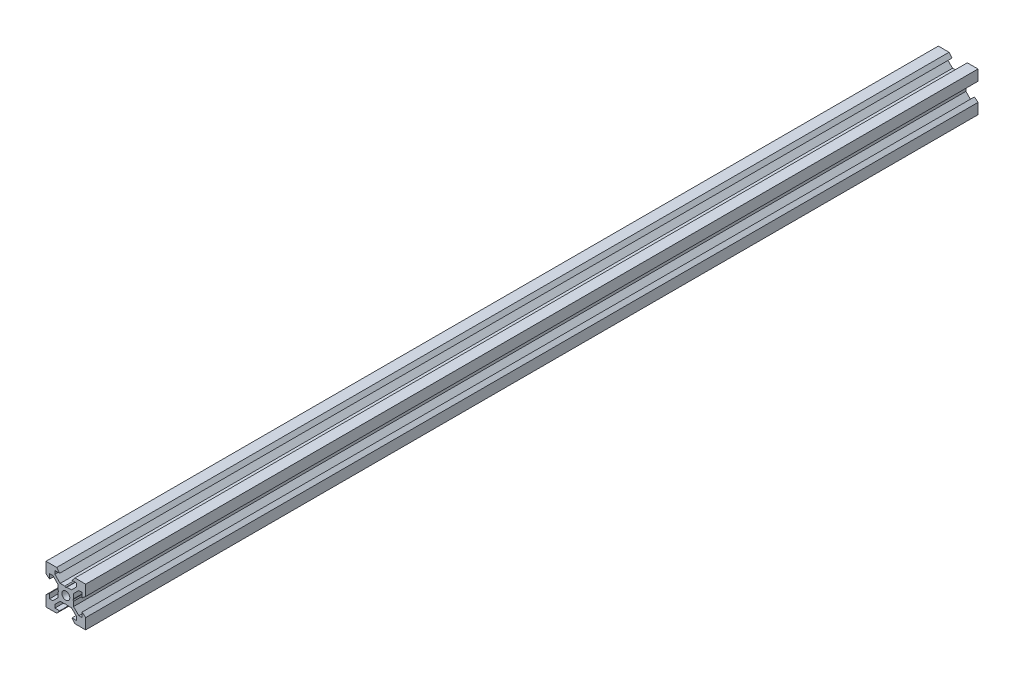
SolidWorks part; units mm, degrees
material "3.3535 (EN-AW 5754)"
ref_plane "Front Plane" through (0, 0, 0) normal (0, 0, 1) x (1, 0, 0)
ref_plane "Top Plane" through (0, 0, 0) normal (0, 1, 0) x (1, 0, 0)
ref_plane "Right Plane" through (0, 0, 0) normal (1, 0, 0) x (0, 0, -1)
sketch "Sketch1" plane through (0, 0, 0) normal (0, 0, 1) x (1, 0, 0)
  line L0 (10, 10) -> (4.6104, 10) construction
  line L1 (10, 10) -> (10, 4.6104) construction
  line L2 (10, -10) -> (10, -4.6104) construction
  line L3 (10, -10) -> (4.6104, -10) construction
  line L4 (10, 10) -> (10, 4.6104)
  line L5 (6.5607, 5.5) -> (8.2, 5.5)
  line L6 (5.5, 8.2) -> (5.5, 6.5607)
  line L7 (10, 10) -> (4.6104, 10)
  line L8 (10, 10) -> (10, 4.6104)
  line L9 (6.5607, 5.5) -> (3.9, 2.8393)
  line L10 (5.5, 6.5607) -> (2.8393, 3.9)
  line L11 (10, 4.6104) -> (8.2, 3.1)
  line L12 (4.6104, 10) -> (3.1, 8.2)
  line L13 (8.2, 3.1) -> (8.2, 5.5)
  line L14 (3.1, 8.2) -> (5.5, 8.2)
  line L15 (-6.5607, 5.5) -> (-8.2, 5.5)
  line L16 (6.5607, -5.5) -> (8.2, -5.5)
  line L17 (3.1, -8.2) -> (5.5, -8.2)
  line L18 (8.2, -3.1) -> (8.2, -5.5)
  line L19 (4.6104, -10) -> (3.1, -8.2)
  line L20 (10, -4.6104) -> (8.2, -3.1)
  line L21 (0.5196, -3.9) -> (0, -3.6)
  line L22 (0.5196, 3.9) -> (0, 3.6)
  line L23 (3.6, 0) -> (3.9, -0.5196)
  line L24 (3.9, 0.5196) -> (3.6, 0)
  line L25 (3.9, 0.5196) -> (3.9, 2.8393)
  line L26 (2.8393, 3.9) -> (0.5196, 3.9)
  line L27 (3.9, -2.8393) -> (3.9, -0.5196)
  line L28 (2.8393, -3.9) -> (0.5196, -3.9)
  line L29 (5.5, -6.5607) -> (2.8393, -3.9)
  line L30 (6.5607, -5.5) -> (3.9, -2.8393)
  line L31 (10, -10) -> (10, -4.6104)
  line L32 (10, -10) -> (4.6104, -10)
  line L33 (5.5, -8.2) -> (5.5, -6.5607)
  line L34 (-6.5607, -5.5) -> (-8.2, -5.5)
  line L35 (10, -10) -> (10, -4.6104)
  line L36 (0, 0) -> (0, 8.2) construction
  line L37 (-10, -10) -> (-4.6104, -10) construction
  line L38 (-10, -10) -> (-10, -4.6104) construction
  line L39 (-10, 10) -> (-10, 4.6104) construction
  line L40 (-10, 10) -> (-4.6104, 10) construction
  line L41 (-10, -10) -> (-10, -4.6104)
  line L43 (-5.5, -8.2) -> (-5.5, -6.5607)
  line L44 (-10, -10) -> (-4.6104, -10)
  line L45 (-10, -10) -> (-10, -4.6104)
  line L46 (-6.5607, -5.5) -> (-3.9, -2.8393)
  line L47 (-5.5, -6.5607) -> (-2.8393, -3.9)
  line L48 (-2.8393, -3.9) -> (-0.5196, -3.9)
  line L49 (-3.9, -2.8393) -> (-3.9, -0.5196)
  line L50 (-2.8393, 3.9) -> (-0.5196, 3.9)
  line L51 (-3.9, 0.5196) -> (-3.9, 2.8393)
  line L52 (-3.9, 0.5196) -> (-3.6, 0)
  line L53 (-3.6, 0) -> (-3.9, -0.5196)
  line L54 (-0.5196, 3.9) -> (0, 3.6)
  line L55 (-0.5196, -3.9) -> (0, -3.6)
  line L56 (-10, -4.6104) -> (-8.2, -3.1)
  line L57 (-4.6104, -10) -> (-3.1, -8.2)
  line L58 (-8.2, -3.1) -> (-8.2, -5.5)
  line L59 (-3.1, -8.2) -> (-5.5, -8.2)
  line L60 (-10, -10) -> (10, -10) construction
  line L61 (-10, -10) -> (-10, 10) construction
  line L62 (-3.1, 8.2) -> (-5.5, 8.2)
  line L63 (-8.2, 3.1) -> (-8.2, 5.5)
  line L64 (-4.6104, 10) -> (-3.1, 8.2)
  line L65 (-10, 4.6104) -> (-8.2, 3.1)
  line L66 (-5.5, 6.5607) -> (-2.8393, 3.9)
  line L67 (-6.5607, 5.5) -> (-3.9, 2.8393)
  line L68 (-10, 10) -> (-10, 4.6104)
  line L69 (-10, 10) -> (-4.6104, 10)
  line L70 (-5.5, 8.2) -> (-5.5, 6.5607)
  line L71 (-10, 10) -> (10, 10) construction
  line L72 (-10, 10) -> (-10, 4.6104)
  line L73 (10, -10) -> (10, 10) construction
  line L74 (-10, -10) -> (10, 10) construction
  line L75 (-10, 10) -> (10, -10) construction
  circle A0 centre (0, 0) radius 2
  dimension "D7" = 4
  dimension "D1" = 20
  dimension "D2" = 5.3896
  dimension "D3" = 4.5
  dimension "D4" = 50
  dimension "D5" = 1.8
  dimension "D6" = 1.5104
  dimension "D8" = 5.5
  dimension "D9" = 120
  dimension "D10" = 0.3
  dimension "D11" = 2.3197
  dimension "D12" = 7.8
  dimension "D13" = 7.8
  dimension "D14" = 1.5
  dimension "D15" = 2.6607
extrude "Boss-Extrude1" add sketch "Sketch1" along normal blind 450 contours L70 L62 L64 L69 L68 L65 L63 L15 L67 L51 L52 L53 L49 L46 L34 L58 L56 L41 L44 L57 L59 L43 L47 L48 L55 L21 L28 L29 L33 L17 L19 L32 L31 L20 L18 L16 L30 L27 L23 L24 L25 L9 L5 L13 L11 L4 L7 L12 L14 L6 L10 region at (9.7172, 7.3052, 0)
